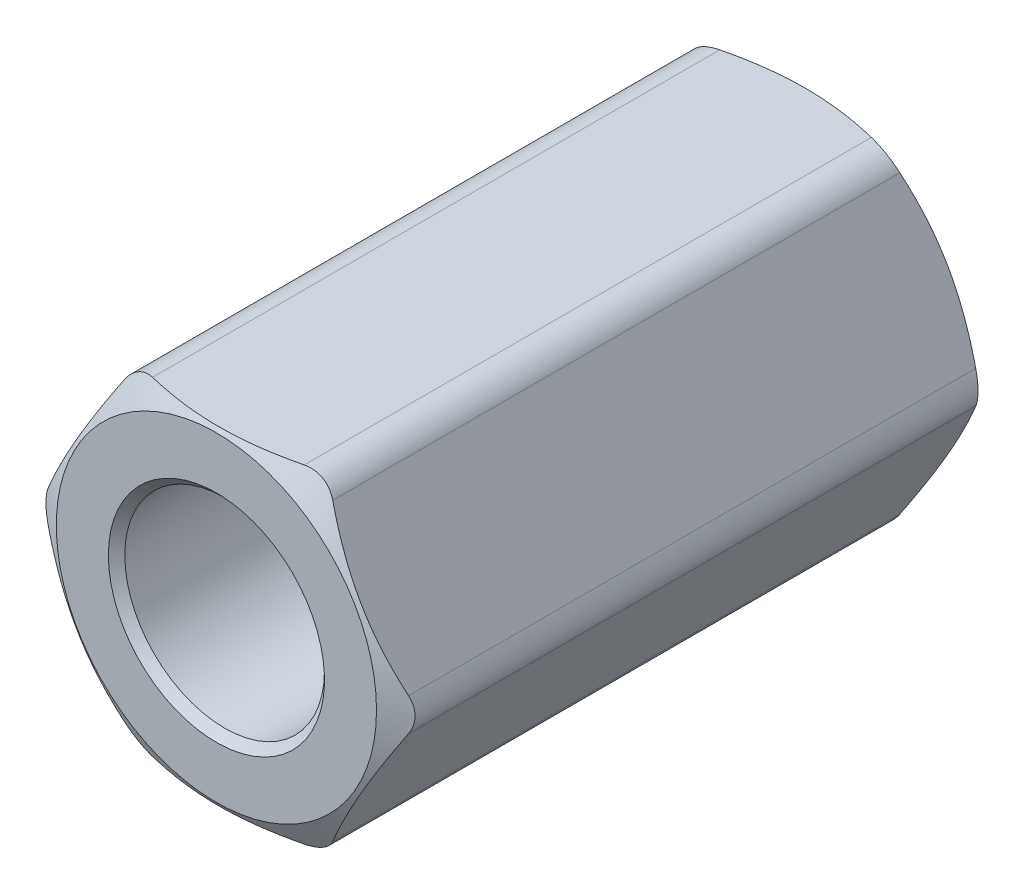
SolidWorks part; units mm, degrees
material "6061-T6 (SS)"
ref_plane "Front Plane" through (0, 0, 0) normal (0, 0, 1) x (1, 0, 0)
ref_plane "Top Plane" through (0, 0, 0) normal (0, 1, 0) x (1, 0, 0)
ref_plane "Right Plane" through (0, 0, 0) normal (1, 0, 0) x (0, 0, -1)
sketch "Sketch1" plane through (0, 0, 0) normal (0, 0, 1) x (1, 0, 0)
  line L1 (2.2914, -3.9688) -> (4.5827, 0)
  line L2 (4.5827, 0) -> (2.2914, 3.9687)
  line L3 (2.2914, 3.9687) -> (-2.2914, 3.9687)
  line L4 (-2.2914, 3.9687) -> (-4.5827, 0)
  line L5 (-4.5827, 0) -> (-2.2914, -3.9688)
  line L6 (-2.2914, -3.9688) -> (2.2914, -3.9688)
  circle A0 centre (0, 0) radius 3.9688 construction
  point P10 (0, -3.9688)
  dimension "Hex Size" = 7.9375
sketch "Sketch2" plane through (0, 0, 0) normal (1, 0, 0) x (0, 0, -1)
  line L0 (7.1437, 0) -> (-7.1437, 0) construction
  line L3 (7.1437, 2.413) -> (7.1437, -2.413) construction
  line L4 (-7.8879, 2.4989) -> (-7.491, 1.8115) construction
  line L5 (-7.491, 1.8115) -> (-7.0941, 2.4989) construction
  line L6 (-7.0941, 2.4989) -> (-7.8879, 2.4989) construction
  line L7 (-7.8383, 2.413) -> (-7.1437, 2.413) construction
  line L8 (-7.5406, 1.8974) -> (-7.4414, 1.8974) construction
  line L9 (-7.491, 1.8974) -> (-7.491, 1.8115) construction
  line L10 (-7.491, 2.413) -> (-7.491, 2.4989) construction
  line L11 (7.1437, 3.9688) -> (-7.1437, 3.9687) construction
  point P6 (0, 3.9688)
  point P9 (7.1437, 0)
  dimension "Thread Length" = 14.2875
  dimension "Thread Size" = 4.826
  dimension "Thread Pitch" = 0.7937
  dimension "Thread Pitch (B)/8" = 0.0992
  dimension "Length" = 14.2875
sketch "Sketch3" plane through (0, 0, 0) normal (1, 0, 0) x (0, 0, -1)
  line L2 (7.1437, 3.9688) -> (7.1437, 2.6114)
  line L3 (7.1437, 2.6114) -> (6.9453, 2.413)
  line L6 (7.1437, 3.9688) -> (7.1437, 2.6114)
  line L8 (6.9453, 2.413) -> (-6.9453, 2.413)
  line L9 (-6.9453, 2.413) -> (-7.1438, 2.6114)
  line L10 (0, 3.9688) -> (7.1437, 3.9688)
  line L11 (-7.1438, 2.6114) -> (-7.1438, 3.9688)
  line L12 (-7.1438, 3.9688) -> (0, 3.9688)
  point P5 (-7.1438, -3.9688)
  dimension "D2" = 0.1984
  dimension "D1" = 45
revolve "Revolve1" add sketch "Sketch3" angle 360 about L0
sketch "Sketch4" plane through (0, 0, 0) normal (0, 0, 1) x (1, 0, 0)
  line L0 (0, 3.9688) -> (0, 2.413) construction
  line L1 (-2.2914, 3.9687) -> (-4.5827, 0)
  line L2 (-4.5827, 0) -> (-2.2914, -3.9688)
  line L3 (-2.2914, -3.9688) -> (2.2914, -3.9688)
  line L4 (2.2914, -3.9688) -> (4.5827, 0)
  line L5 (4.5827, 0) -> (2.2914, 3.9687)
  line L6 (2.2914, 3.9687) -> (-2.2914, 3.9687)
  line L7 (2.2914, -3.9688) -> (4.5827, 0) construction
  circle A0 centre (0, 0) radius 3.9688 construction
  circle A1 centre (0, 0) radius 3.1909
  circle A2 centre (0, 0) radius 3.9688 construction
  point P16 (0, 3.1909)
extrude "Boss-Extrude1" add sketch "Sketch4" against normal mid plane 14.2875
sketch "Sketch5" plane through (0, 0, 7.1438) normal (0, 0, 1) x (1, 0, 0)
  line L0 (0, 2.413) -> (0, -2.413) construction
  line L1 (0, 2.413) -> (0, -2.413) construction
  circle A0 centre (0, 0) radius 3.8695
  point P11 (0, -2.413)
  dimension "D1" = 7.7391
extrude "Cut-Extrude1" cut sketch "Sketch5" against normal through all draft 60 flip side to cut
sketch "Sketch6" plane through (0, 0, -7.1437) normal (0, 0, -1) x (-1, 0, 0)
  circle A0 centre (0, 0) radius 3.8695
  circle A1 centre (0, 0) radius 3.8695 construction
extrude "Cut-Extrude2" cut sketch "Sketch6" against normal through all draft 60 flip side to cut
fillet "Fillet1" radius 0.7937 6 edges at (2.2914, 3.9687, 0) (-4.5827, 0, 0) (-2.2914, -3.9688, 0) (2.2914, -3.9688, 0) (4.5827, 0, 0) (-2.2914, 3.9687, 0)
sketch "Drawing 1" plane through (0, 0, 0) normal (1, 0, 0) x (0, 0, -1)
  line L0 (7.1437, -2.413) -> (-7.1438, -2.413) construction
  line L1 (7.1437, 2.413) -> (-7.1438, 2.413) construction
  line L3 (7.1437, 0) -> (-7.1437, 0) construction
sketch "Sketch7" [suppressed] plane through (0, 0, -7.1437) normal (0, 0, -1) x (-1, 0, 0)
  circle A0 centre (0, 0) radius 2.6114
extrude "Boss-Extrude2" [suppressed] add sketch "Sketch7" along normal up to surface (14.2875 mm away)
sketch "Sketch8" [suppressed] plane through (0, 0, 0) normal (1, 0, 0) x (0, 0, -1)
  line L0 (7.1437, 0) -> (-7.1437, 0) construction
  line L1 (7.1437, 2.413) -> (-7.1437, 2.413)
  line L2 (7.1437, 2.413) -> (7.1437, 0)
  line L3 (7.1437, 0) -> (-7.1437, 0)
  line L4 (-7.1437, 2.413) -> (-7.1437, 0)
revolve "Revolve2" [suppressed] add sketch "Sketch8" angle 360 about L0
sketch "Sketch9" [suppressed] plane through (0, 0, 7.1437) normal (0, 0, 1) x (1, 0, 0)
  circle A0 centre (0, 0) radius 2.413
  circle A1 centre (0, 0) radius 2.413 construction
sketch "Sketch10" [suppressed] plane through (0, 0, 0) normal (1, 0, 0) x (0, 0, -1)
  line L0 (-7.5406, 1.8974) -> (-7.4414, 1.8974)
  line L1 (-7.4414, 1.8974) -> (-7.1189, 2.456)
  line L2 (-7.491, 1.8115) -> (-7.0941, 2.4989) construction
  line L3 (-7.1189, 2.456) -> (-7.8631, 2.456)
  line L4 (-7.8879, 2.4989) -> (-7.491, 1.8115) construction
  line L5 (-7.8631, 2.456) -> (-7.5406, 1.8974)
  line L6 (-7.491, 2.413) -> (-7.491, 2.4989) construction
  point P12 (-7.491, 2.456)
curve "Helix/Spiral1" [suppressed] pitch 0.7937 height 11.9062 turns 15
sweep "Cut-Sweep1" [suppressed] cut profiles "Sketch10" path "Helix/Spiral1"
pattern_linear "LPattern1" [suppressed] count 2 spacing 10.3187 of bodies 114
combine bodies "Combine1" [suppressed] operation type subtract main body 113 bodies to subtract 119
ref_plane "Plane1" [suppressed] through (0, 0, 6.9453) normal (0, 0, 1) x (1, 0, 0)
sketch "Sketch11" [suppressed] plane through (0, 0, 7.1438) normal (0, 0, 1) x (1, 0, 0)
  circle A0 centre (0, 0) radius 2.6114
extrude "Cut-Extrude3" [suppressed] cut sketch "Sketch11" against normal through all draft 45
sketch "Sketch12" [suppressed] plane through (0, 0, 6.9453) normal (0, 0, 1) x (1, 0, 0)
  circle A0 centre (0, 0) radius 2.4638
  circle A1 centre (0, 0) radius 2.413 construction
  dimension "D1" = 0.0508
extrude "Cut-Extrude4" [suppressed] cut sketch "Sketch12" against normal through all draft 45
mirror "Mirror1" [suppressed] about plane through (0, 0, 0) normal (0, 0, 1)
equation "\"Thread Pitch (B)/8@Sketch2\" = \"Thread Pitch@Sketch2\" / 8"
equation "\"D1@Fillet1\" = \"Hex Size@Sketch1\" * .1"
equation "\"D3@Helix/Spiral1\"= \"segment length\" + \"Thread Pitch@Sketch2\""
equation "\"D4@Helix/Spiral1\" = \"Thread Pitch@Sketch2\""
equation "\"Thread Length@Sketch2\"=\"Length@Sketch2\""
equation "\"D1@Boss-Extrude1\" = \"Length@Sketch2\""
equation "\"D2@Sketch3\"=\"Thread Pitch@Sketch2\"*.25"
equation "\"D1@Sketch5\"=\"Hex Size@Sketch1\"*.975"
equation "\"thread count\"= \"Length@Sketch2\" * .75 / \"Thread Pitch@Sketch2\""
equation "\"rounded thread count\"= IIF ( \"thread count\" - int ( \"thread count\" ) > 0 , int ( \"thread count\" ) + 1 , \"thread count\" )"
equation "\"segment length\"= \"Thread Pitch@Sketch2\" * \"rounded thread count\""
equation "\"D3@LPattern1\"= \"segment length\" - \"thread pitch@sketch2\""
